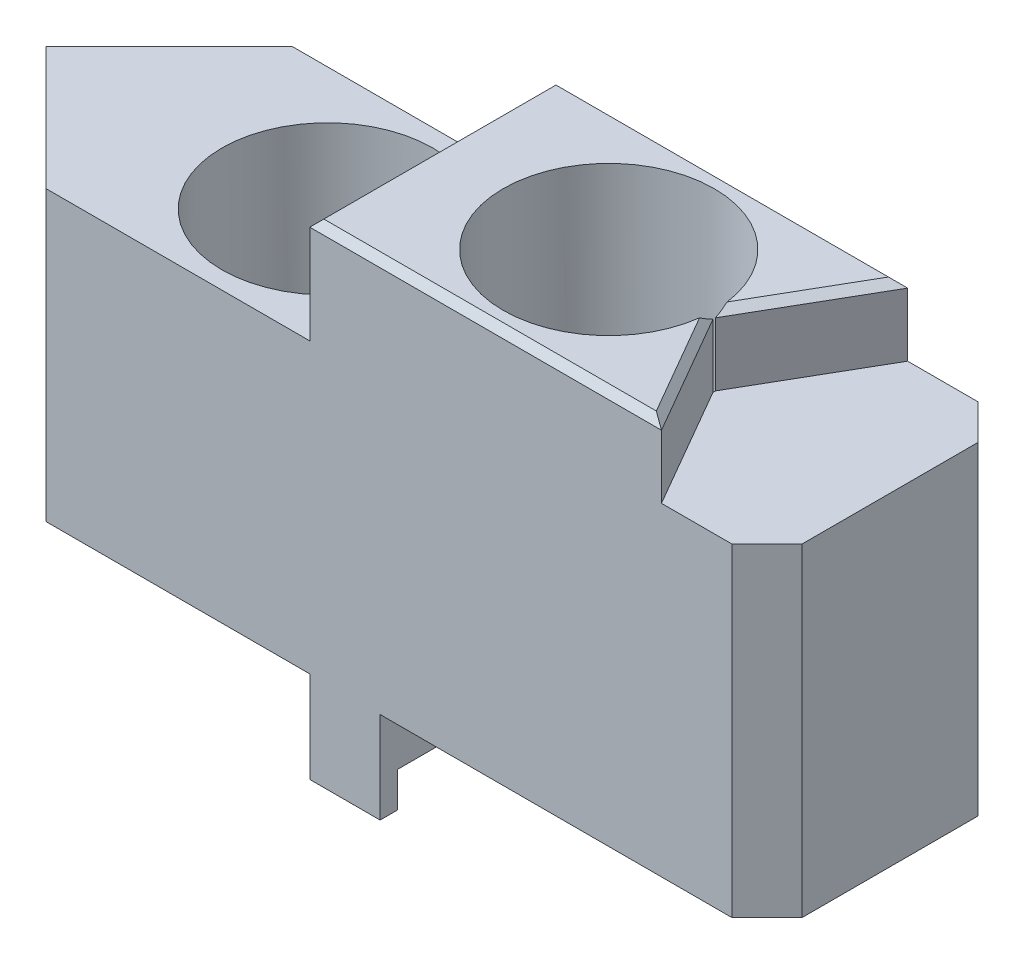
SolidWorks part; units mm, degrees
material "6061"
ref_plane "前视" through (0, 0, 0) normal (0, 0, 1) x (1, 0, 0)
ref_plane "上视" through (0, 0, 0) normal (0, 1, 0) x (1, 0, 0)
ref_plane "右视" through (0, 0, 0) normal (1, 0, 0) x (0, 0, -1)
sketch "草图1" plane through (0, 0, 0) normal (0, 0, 1) x (1, 0, 0)
  line L1 (-12, -6.9) -> (12, -6.9)
  line L2 (-12, -6.9) -> (-12, 6.9)
  line L3 (-12, 6.9) -> (12, 6.9)
  line L4 (12, -6.9) -> (12, 6.9)
  line L5 (-12, -6.9) -> (12, 6.9) construction
  line L6 (-12, 6.9) -> (12, -6.9) construction
  point P0 (0, 0)
  dimension "D1" = 13.8
  dimension "D2" = 24
extrude "凸台-拉伸1" add sketch "草图1" along normal mid plane 7
hole_wizard "打孔尺寸根据内六角圆柱头螺钉的类型1" positions "草图3" profile "草图2" counterbore size "M3" standard "Gb" end condition through all
sketch "草图3" plane through (0, 6.9, 0) normal (0, 1, 0) x (1, 0, 0)
  line L0 (12, 0) -> (-4.7048, 0) construction
  line L1 (12, -3.5) -> (12, 3.5) construction
  point P0 (4, 0)
  point P11 (-4, 0)
  dimension "D1" = 8
  dimension "D2" = 8
sketch "草图2" plane through (4, 6.9, 0) normal (1, 0, 0) x (0, 0, 1)
  line L0 (0, 0) -> (0, 13.8)
  line L1 (0, 13.8) -> (1.7, 13.8)
  line L3 (1.7, 13.8) -> (1.7, 9)
  line L4 (1.7, 9) -> (3, 9)
  line L5 (3, 9) -> (3, 0)
  line L7 (3, 0) -> (0, 0)
  line L11 (0, -6.35) -> (0, 107.95) construction
  dimension "通孔孔直径" = 3.4
  dimension "通孔孔深度" = 13.8
  dimension "柱形沉头孔直径" = 6
  dimension "柱形沉头孔深度" = 9
sketch "草图4" plane through (0, 6.9, 0) normal (0, 1, 0) x (1, 0, 0)
  line L0 (4, 0) -> (12, 0) construction
  line L1 (12, -3.5) -> (12, 3.5) construction
  line L2 (9, 3.5) -> (6.9793, 0)
  line L3 (12, 3.5) -> (-12, 3.5) construction
  line L4 (6.9793, 0) -> (9, -3.5)
  line L5 (12, -3.5) -> (-12, -3.5) construction
  line L6 (9, -3.5) -> (12, -3.5)
  line L7 (12, -3.5) -> (12, 3.5)
  line L8 (12, 3.5) -> (9, 3.5)
  dimension "D1" = 120
  dimension "D2" = 3
extrude "切除-拉伸1" cut sketch "草图4" against normal blind 2
sketch "草图5" plane through (0, 0, 3.5) normal (0, 0, 1) x (1, 0, 0)
  line L0 (-4, -1.3837) -> (4, -1.3837) construction
  line L1 (-4, -6.9) -> (-4, -2.1) construction
  line L2 (4, -6.9) -> (4, -2.1) construction
  line L3 (0, -1.3837) -> (0, -11.2797) construction
  line L5 (12, -6.9) -> (1, -6.9)
  line L6 (12, -6.9) -> (12, -4.3)
  line L7 (12, -4.3) -> (1, -4.3)
  line L8 (1, -6.9) -> (1, -4.3)
  line L9 (-12, -6.9) -> (-1, -6.9)
  line L10 (-12, -6.9) -> (-12, -4.3)
  line L11 (-12, -4.3) -> (-1, -4.3)
  line L12 (-1, -6.9) -> (-1, -4.3)
  line L17 (-1, -2.1) -> (-1, 6.9) construction
  line L18 (-12, 6.9) -> (-1, 6.9)
  line L19 (-12, 6.9) -> (-12, 3.9)
  line L20 (-12, 3.9) -> (-1, 3.9)
  line L21 (-1, 6.9) -> (-1, 3.9)
  line L22 (9, 4.9) -> (12, 4.9) construction
  dimension "D1" = 2
  dimension "D2" = 2.6
  dimension "D5" = 1
extrude "切除-拉伸2" cut sketch "草图5" against normal through all
sketch "草图6" plane through (0, -6.9, 0) normal (0, -1, 0) x (1, 0, 0)
  line L0 (-1, 0) -> (1, 0) construction
  line L1 (-1, -3.5) -> (-1, 3.5) construction
  line L2 (1, -3.5) -> (1, 3.5) construction
  line L4 (-1, -3) -> (1, -3)
  line L5 (-1, -3) -> (-1, 3)
  line L6 (-1, 3) -> (1, 3)
  line L7 (1, -3) -> (1, 3)
  line L8 (-1, -3) -> (1, 3) construction
  line L9 (-1, 3) -> (1, -3) construction
  line L10 (-1, -3.5) -> (-1, 3.5) construction
  point P6 (0, 0)
  dimension "D1" = 6
extrude "切除-拉伸3" cut sketch "草图6" against normal blind 1
sketch "草图7" plane through (0, 4.9, 0) normal (0, 1, 0) x (1, 0, 0)
  line L0 (6.9998, -0.0355) -> (9, -3.5)
  line L1 (9, -3.5) -> (12.4641, -3.5)
  line L2 (9, -3.5) -> (12, -3.5) construction
  line L3 (12.4641, -3.5) -> (11.1073, -1.15)
  line L4 (4, 0) -> (8.8091, 0) construction
  line L5 (12.4641, 3.5) -> (11.1073, 1.15)
  line L6 (9, 3.5) -> (12.4641, 3.5)
  line L7 (6.9998, 0.0355) -> (9, 3.5)
  line L8 (11.1073, 1.15) -> (11.1073, -1.15)
  arc A0 (6.9998, -0.0355) -> (6.9998, 0.0355) centre (4, 0) ccw construction
  circle A1 centre (4, 0) radius 3 construction
  arc A2 (6.9998, -0.0355) -> (6.9998, 0.0355) centre (4, 0) ccw
  dimension "D1" = 3
  dimension "D2" = 2.3
extrude "切除-拉伸4" [suppressed] cut sketch "草图7" against normal blind 1.2
chamfer "倒角1" distance 3.5 angle 45 2 edges at (-12, -0.2, -3.5) (-12, -0.2, 3.5)
chamfer "倒角2" distance 0.2 angle 45 5 edges at (7.9999, 6.9, 1.7678) (7.9999, 6.9, -1.7678) (4, 6.9, -3.5) (4, 6.9, 3.5) (-1, 6.9, 0)
chamfer "倒角3" distance 1 angle 45 2 edges at (12, 0.3, -3.5) (12, 0.3, 3.5)
